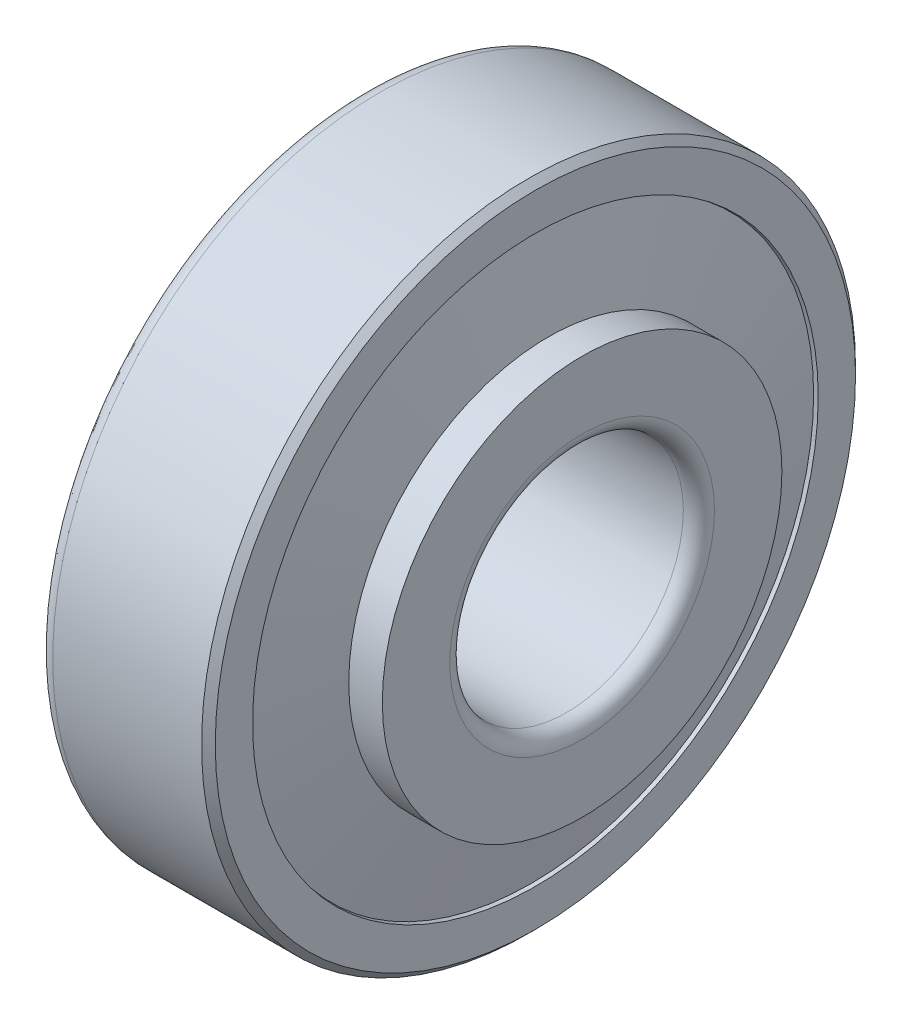
SolidWorks part; units mm, degrees
revolve "OuterRace" add sketch "OutRacSke" angle 360 about L5 other way angle 28.04 reverse direction yes
sketch "OutRacSke" plane through (0, 0, 0) normal (0, 0, 1) x (1, 0, 0)
  line L0 (-3, 18.1648) -> (-14, 16.136)
  line L1 (-14, 16.136) -> (-14, 20)
  line L2 (-13, 21) -> (-3.44, 21)
  line L3 (-3.44, 21) -> (-3, 20.56)
  line L4 (-3, 20.56) -> (-3, 18.1648)
  line L5 (-42.5, 0) -> (42.5, 0) construction
  arc A0 (-14, 20) -> (-13, 21) centre (-13, 20) cw
  dimension "D8" = 45
  dimension "Tangle" = 10.45
ref_plane "Plane1" through (0, 0, 0) normal (0, 0, 1) x (1, 0, 0)
ref_plane "Plane2" through (0, 0, 0) normal (0, 1, 0) x (1, 0, 0)
ref_plane "Plane3" through (0, 0, 0) normal (1, 0, 0) x (0, 0, -1)
sketch "Clipboard" plane through (0, 0, 0) normal (0, 0, 1) x (1, 0, 0)
  line L0 (0, 0) -> (10, 0) construction
  line L1 (0, 0) -> (32.2523, -1.1263)
  line L2 (0, 0) -> (14.9909, 0.5235)
  line L3 (0, 0) -> (41.9744, -1.4658)
  line L4 (0, 0) -> (-9.8985, -0.1728)
  line L5 (0, 0) -> (-6.075, 14)
  dimension "Roller_diameter" = 6.075
  dimension "cyl_len" = 9.9
sketch "RolDetSke" plane through (0, 0, 0) normal (0, 0, 1) x (1, 0, 0)
  line L0 (-12.4491, 13.4149) -> (-13, 16.402)
  line L1 (-12.4491, 13.4149) -> (-2.7133, 15.2106)
  line L2 (-3.2642, 18.1977) -> (-2.7133, 15.2106)
  line L4 (-66.9322, 3.3662) -> (-22.1176, 11.6317) construction
  line L5 (-3.2642, 18.1977) -> (-13, 16.402)
  line L9 (-3, 18.1648) -> (-14, 16.136) construction
  dimension "Roller_diameter" = 6.075
  dimension "dy" = 16.402
  dimension "D2" = 13
  dimension "cyl_len" = 9.9
revolve "RollerDetailed" [suppressed] add sketch "RolDetSke" angle 360 about L4 reverse direction yes
sketch "RolSimSke" plane through (0, 0, 0) normal (0, 0, 1) x (1, 0, 0)
  line L0 (0, 0) -> (-32, 0) construction
  line L1 (-13, 16.402) -> (-3.2642, 18.1977)
  line L2 (-13, 16.402) -> (-11.8981, 10.4278)
  line L3 (-11.8981, 10.4278) -> (-2.1623, 12.2234)
  line L4 (-3.2642, 18.1977) -> (-2.1623, 12.2234)
  dimension "Roller_diameter" = 6.075
  dimension "dy" = 16.402
  dimension "dx" = 13
  dimension "Tangle" = 10.45
revolve "RollersSimplified" add sketch "RolSimSke" angle 360 about L0
ref_axis "Axis1" through (-50, 0, 0) along (1, 0, 0)
pattern_circular "RollersDetailed" [suppressed] count 2 every 180 about axis through (-50, 0, 0) along (1, 0, 0)
sketch "InsRacSke" plane through (0, 0, 0) normal (0, 0, 1) x (1, 0, 0)
  line L0 (-11.9486, 10.7316) -> (-13, 10.7316)
  line L1 (-14, 20) -> (-14, -20) construction
  line L2 (-13, 10.7316) -> (-13, 7.94)
  line L3 (-13, 7.94) -> (-12.56, 7.5)
  line L4 (-12.56, 7.5) -> (-1, 7.5)
  line L5 (0, 8.5) -> (0, 12.8309)
  line L6 (0, 12.8309) -> (-2.1568, 12.8309)
  line L7 (-2.1568, 12.8309) -> (-2.1568, 12.2234)
  line L8 (-2.1568, 12.2234) -> (-11.8926, 10.4278)
  line L9 (-11.8926, 10.4278) -> (-11.9486, 10.7316)
  line L10 (-42.5, 0) -> (42.5, 0) construction
  arc A0 (-1, 7.5) -> (0, 8.5) centre (-1, 8.5) ccw
  dimension "Tangle" = 10.45
  dimension "cyl_len" = 9.9
  dimension "dy" = 10.4278
  dimension "dx" = 11.8926
  dimension "D11" = 45
  dimension "D2" = 14
revolve "InnerRace" add sketch "InsRacSke" angle 360 about L10 reverse direction yes
sketch "CagSpiSke" plane through (0, 0, 0) normal (0, 0, 1) x (1, 0, 0)
  line L3 (-2.2265, 15.2187) -> (-12.4491, 13.3333)
  line L4 (-12.7739, 12.8616) -> (-12.627, 12.065)
  line L6 (-42.5, 0) -> (42.5, 0) construction
  arc A1 (-12.4491, 13.3333) -> (-12.7739, 12.8616) centre (-12.3756, 12.935) ccw
  dimension "Tangle" = 10.45
  dimension "radius" = 0.405
  dimension "dx" = 12.4491
  dimension "dy" = 13.3333
  dimension "offset" = 1.215
revolve "CageSpine" [suppressed] add sketch "CagSpiSke" angle 0.001 about L6 wall 1.0125
equation "\"OD@OutRacSke\" = \"Race_OD@Clipboard\""
equation "\"cup_SID@OutRacSke\" = \"Race_ID@Clipboard\""
equation "\"chamfer@OutRacSke\" = \"cup_width@OutRacSke\" / 25"
equation "\"offset@OutRacSke\" = \"OA_width@Clipboard\""
equation "\"D2@RolDetSke\" = \"offset@OutRacSke\" - \"cup_radius@OutRacSke\""
equation "\"dy@RolDetSke\" =  ( ( \"Race_ID@Clipboard\" / 2 ) + ( \"cup_radius@OutRacSke\" ) * tan(\"Tangle@OutRacSke\" * 3.141592654/180) ) * 1.005"
equation "\"cyl_len@RolDetSke\" = \"cyl_len@Clipboard\""
equation "\"Roller_diameter@RolDetSke\" = \"Roller_diameter@Clipboard\""
equation "\"dx@RolSimSke\" = \"offset@OutRacSke\" - \"cup_radius@OutRacSke\""
equation "\"dy@RolSimSke\" =  ( ( \"Race_ID@Clipboard\" / 2 ) + ( \"cup_radius@OutRacSke\" ) * tan(\"Tangle@OutRacSke\" * 3.141592654/180) ) * 1.005"
equation "\"Cyl_Len@RolSimSke\" = \"cyl_len@Clipboard\""
equation "\"Roller_diameter@RolSimSke\" = \"Roller_diameter@Clipboard\""
equation "\"Bore@InsRacSke\" = \"Bore@Clipboard\""
equation "\"Tangle@InsRacSke\" = \"Tangle@OutRacSke\""
equation "\"cyl_len@InsRacSke\" = \"cyl_len@Clipboard\""
equation "\"chamfer@InsRacSke\" = \"chamfer@OutRacSke\""
equation "\"D2@InsRacSke\" = \"OA_width@Clipboard\""
equation "\"dx@InsRacSke\" = \"offset@OutRacSke\" - \"cup_radius@OutRacSke\" -  (  \"Roller_diameter@Clipboard\" * 1.005 )  * sin(\"Tangle@InsRacSke\" * 3.141592654/180)"
equation "\"dy@InsRacSke\" = ( ( \"Race_ID@Clipboard\" / 2 ) + ( \"cup_radius@OutRacSke\" ) * tan(\"Tangle@OutRacSke\" * 3.141592654/180) ) * 1.005 -  ( \"Roller_diameter@Clipboard\" )  * cos(\"Tangle@InsRacSke\" * 3.141592654/180) "
equation "\"front_groove@InsRacSke\" = \"Groove_dp@InsRacSke\" / 2"
equation "\"Tangle@CagSpiSke\" = \"Tangle@OutRacSke\""
equation "\"dx@CagSpiSke\" = ( \"offset@OutRacSke\" - \"cup_radius@OutRacSke\" ) -  (  \"Roller_diameter@Clipboard\" / 2  )  * sin(\"Tangle@InsRacSke\" * 3.141592654/180)"
equation "\"dy@CagSpiSke\" = ( ( \"Race_ID@Clipboard\" / 2 ) + ( \"cup_radius@OutRacSke\" ) * tan(\"Tangle@OutRacSke\" * 3.141592654/180) )  -  ( \"Roller_diameter@Clipboard\" / 2 )  * cos(\"Tangle@InsRacSke\" * 3.141592654/180) "
equation "\"length@CagSpiSke\" = \"cyl_len@Clipboard\" * 1.05"
equation "\"offset@CagSpiSke\" = \"Roller_diameter@Clipboard\" / 5"
equation "\"radius@CagSpiSke\" = \"offset@CagSpiSke\" / 3"
equation "\"D3@CageSpine\" = \"Roller_diameter@Clipboard\" / 6"
equation "\"Max_count@Clipboard\" = int( 3.14159265 / atn(( \"Roller_diameter@Clipboard\" / 2) / sqr( \"dy@CagSpiSke\"  *  \"dy@CagSpiSke\" - ( \"Roller_diameter@Clipboard\" / 2) *  ( \"Roller_diameter@Clipboard\" / 2))))"
equation "\"Max_count@Clipboard\" = ((sgn( \"Max_count@Clipboard\" - \"Count@Clipboard\" )-1)*( \"Max_count@Clipboard\" - \"Count@Clipboard\" ))/-2+ \"Count@Clipboard\""
equation "\"Count@RollersDetailed\" = int( \"Show_count@Clipboard\" ) "
equation "\"Count@RollersDetailed\" = ((sgn( \"Count@RollersDetailed\" - \"Max_count@Clipboard\" )-1)*( \"Count@RollersDetailed\" - \"Max_count@Clipboard\" ))/-2+ \"Max_count@Clipboard\""
equation "\"Count@RollersDetailed\" = ((sgn( \"Count@RollersDetailed\" - \"Min_count@Clipboard\" )+1)*( \"Count@RollersDetailed\" - \"Min_count@Clipboard\"))/2 +\"Min_count@Clipboard\""
equation "\"Angle@RollersDetailed\" = 360.0 / \"Max_count@Clipboard\""
equation "\"Angle@CageSpine\" =  \"Angle@RollersDetailed\" * ( \"Count@RollersDetailed\" -1 + int( \"Count@RollersDetailed\" / \"Max_count@Clipboard\" ) )  + 0.001 -  int( \"Count@RollersDetailed\" / \"Max_count@Clipboard\" ) * 0.001"
equation "\"Angle@CageSpine\" =  \"Angle@CageSpine\" * int( \"Min_count@Clipboard\" / 2) + int(1 / \"Min_count@Clipboard\")  * 0.001"
equation "\"Tangle@RolSimSke\" = \"Tangle@OutRacSke\""
